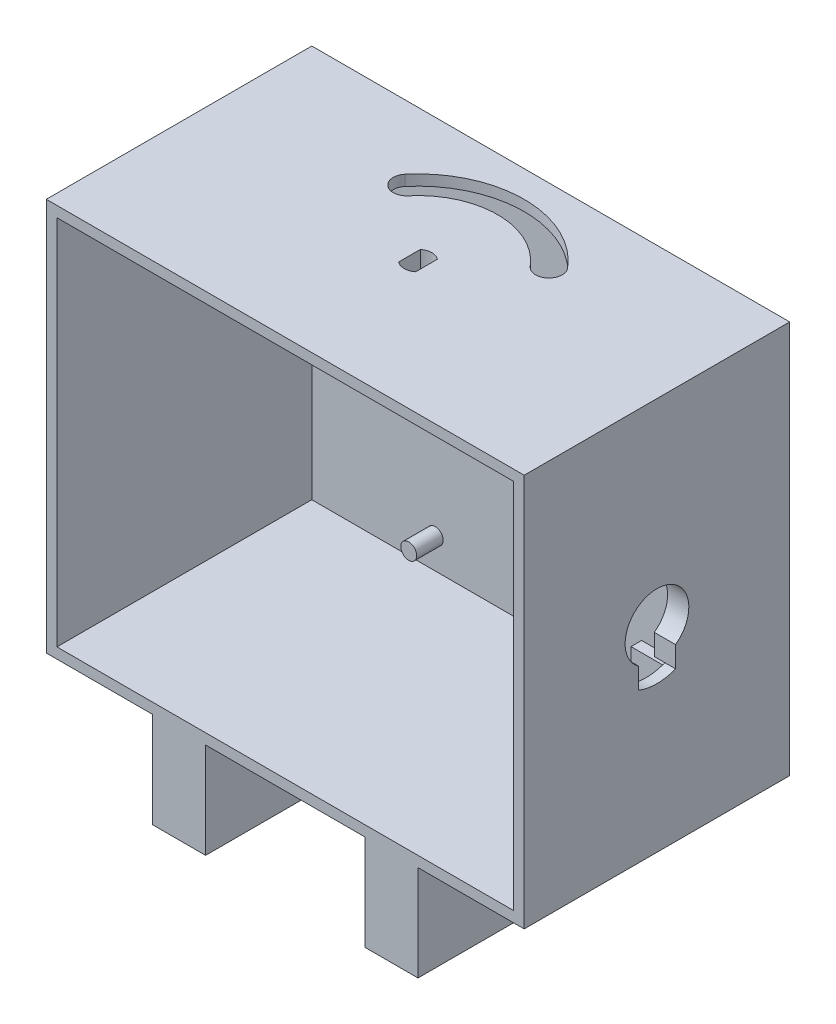
SolidWorks part; units mm, degrees
ref_plane "Front Plane" through (0, 0, 0) normal (0, 0, 1) x (1, 0, 0)
ref_plane "Top Plane" through (0, 0, 0) normal (0, 1, 0) x (1, 0, 0)
ref_plane "Right Plane" through (0, 0, 0) normal (1, 0, 0) x (0, 0, -1)
sketch "Sketch1" plane through (0, 0, 0) normal (0, 0, 1) x (1, 0, 0)
  line L0 (45, 37) -> (-45, 37)
  line L1 (43, -35) -> (-43, -35)
  line L2 (43, -35) -> (43, 35)
  line L3 (43, 35) -> (-43, 35)
  line L4 (-43, -35) -> (-43, 35)
  line L5 (43, -35) -> (-43, 35) construction
  line L6 (43, 35) -> (-43, -35) construction
  line L7 (-45, -37) -> (-45, 37)
  line L8 (45, -37) -> (-45, -37)
  line L9 (45, -37) -> (45, 37)
  line L10 (-15, -46) -> (15, -46) construction
  line L11 (-25, -37) -> (-15, -37)
  line L12 (-25, -37) -> (-25, -55)
  line L13 (-25, -55) -> (-15, -55)
  line L14 (-15, -37) -> (-15, -55)
  line L15 (15, -37) -> (25, -37)
  line L16 (15, -37) -> (15, -55)
  line L17 (15, -55) -> (25, -55)
  line L18 (25, -37) -> (25, -55)
  line L19 (0, -46) -> (0, 0) construction
  point P0 (0, 0)
  dimension "D1" = 70
  dimension "D2" = 86
  dimension "D4" = 18
  dimension "D5" = 10
  dimension "D6" = 18
  dimension "D7" = 10
  dimension "D8" = 30
  dimension "D3" = 2
extrude "Boss-Extrude1" add sketch "Sketch1" along normal mid plane 50 contours L8 L9 L0 L7 L1 L4 L3 L2 region at (43.8348, 0, 0)
extrude "Boss-Extrude2" add sketch "Sketch1<3>" against normal blind 25 from surface contours L14 L8 L12 L13 | L18 L8 L16 L17 region at (20, -46, 0) region at (-20, -46, 0) starting at face at (0, 0, 25)
sketch "Sketch1<3>" plane through (0, 0, 0) normal (0, 0, 1) x (1, 0, 0) same geometry as "Sketch1"
sketch "Sketch2" plane through (0, 0, -25) normal (0, 0, -1) x (-1, 0, 0)
  line L0 (-43, -35) -> (43, -35) construction
  line L1 (43, -35) -> (43, 35) construction
  line L2 (-43, 35) -> (43, 35) construction
  line L3 (-43, -35) -> (-43, 35) construction
  line L4 (-43, -35) -> (43, -35)
  line L5 (43, -35) -> (43, 35)
  line L6 (-43, 35) -> (43, 35)
  line L7 (-43, -35) -> (-43, 35)
extrude "Boss-Extrude3" add sketch "Sketch2" against normal blind 2
sketch "Sketch3" plane through (0, 37, 0) normal (0, 1, 0) x (1, 0, 0)
  line L1 (1.6, -2.0494) -> (-1.6, -2.0494)
  line L2 (1.6, -2.0494) -> (1.6, 2.0494)
  line L3 (1.6, 2.0494) -> (-1.6, 2.0494)
  line L4 (-1.6, -2.0494) -> (-1.6, 2.0494)
  line L5 (1.6, -2.0494) -> (-1.6, 2.0494) construction
  line L6 (1.6, 2.0494) -> (-1.6, -2.0494) construction
  circle A0 centre (0, 0) radius 2.6
  circle A1 centre (0, 0) radius 4.1
  dimension "D1" = 5.2
  dimension "D3" = 1.5
  dimension "D2" = 3.2
extrude "Cut-Extrude1" cut sketch "Sketch3" against normal up to surface (2 mm away) contours L3 A0 | L4 L1 L2 L3 | L1 A0 region at (0, 37, 2.2718) region at (0, 37, 0) region at (0, 37, -2.2718) up to face at (0, 35, 1)
extrude "Boss-Extrude4" add sketch "Sketch3<4>" against normal blind 7.5 contours A1 A0 | L2 A0 | L4 A0 region at (2.0074, 37, 0) region at (-2.0074, 37, 0) region at (-3.984, 37, 0)
sketch "Sketch3<4>" plane through (0, 37, 0) normal (0, 1, 0) x (1, 0, 0) same geometry as "Sketch3"
sketch "Sketch4" plane through (45, 0, 0) normal (1, 0, 0) x (0, 0, -1)
  line L0 (0, -6) -> (0, -9.5) construction
  line L1 (3.5, -4.8734) -> (3.5, -8.8318)
  line L2 (-3.5, -4.8734) -> (-3.5, -8.8318)
  line L3 (0, -23) -> (0, -9.5) construction
  line L4 (8.1, 10.5) -> (-8.1, 10.5)
  line L5 (8.1, 10.5) -> (8.1, 12.5)
  line L6 (8.1, 12.5) -> (-8.1, 12.5)
  line L7 (-8.1, 10.5) -> (-8.1, 12.5)
  line L8 (8.1, 10.5) -> (-8.1, 12.5) construction
  line L9 (8.1, 12.5) -> (-8.1, 10.5) construction
  line L10 (8.1, -24) -> (-8.1, -24)
  line L11 (8.1, -24) -> (8.1, -22)
  line L12 (8.1, -22) -> (-8.1, -22)
  line L13 (-8.1, -24) -> (-8.1, -22)
  line L14 (8.1, -24) -> (-8.1, -22) construction
  line L15 (8.1, -22) -> (-8.1, -24) construction
  line L16 (-8.1, -22) -> (-6.1, -22)
  line L17 (-8.1, -22) -> (-8.1, -12)
  line L18 (-8.1, -12) -> (-6.1, -12)
  line L19 (-6.1, -22) -> (-6.1, -12)
  line L20 (8.1, -12) -> (6.1, -12)
  line L21 (-8.1, 10.5) -> (-6.1, 10.5)
  line L22 (-8.1, 10.5) -> (-8.1, 8.5)
  line L23 (-8.1, 8.5) -> (-6.1, 8.5)
  line L24 (-6.1, 10.5) -> (-6.1, 8.5)
  line L25 (6.1, -22) -> (6.1, -12)
  line L26 (8.1, -22) -> (6.1, -22)
  line L27 (8.1, -22) -> (8.1, -12)
  line L28 (8.1, 8.5) -> (6.1, 8.5)
  line L29 (6.1, 10.5) -> (6.1, 8.5)
  line L30 (8.1, 10.5) -> (6.1, 10.5)
  line L31 (8.1, 10.5) -> (8.1, 8.5)
  circle A0 centre (0, 0) radius 6
  circle A1 centre (0, 0) radius 9.5
  point P10 (0, 11.5)
  point P16 (0, -23)
  dimension "D1" = 12
  dimension "D2" = 3.5
  dimension "D3" = 7
  dimension "D4" = 10.5
  dimension "D5" = 16.2
  dimension "D6" = 2
  dimension "D7" = 32.5
  dimension "D8" = 2
  dimension "D9" = 10
  dimension "D10" = 2
extrude "Cut-Extrude2" cut sketch "Sketch4" against normal up to surface (2 mm away) contours A0 | L2 A1 L1 A0 region at (45, -7.4505, 0) region at (45, 0, 0) up to face at (43, 0, 1)
extrude "Boss-Extrude5" add sketch "Sketch4<3>" against normal blind 2 from surface contours L1 A1 L2 A0 region at (45, -2.8591, -5.5735) starting at face at (43, -4.3013, 0)
sketch "Sketch4<3>" plane through (45, 0, 0) normal (1, 0, 0) x (0, 0, -1) same geometry as "Sketch4"
extrude "Boss-Extrude6" add sketch "Sketch4<4>" against normal blind 9 from surface contours L7 L4 L5 L6 | L12 L19 L18 L17 | L13 L10 L11 L12 | L12 L27 L20 L25 | L24 L4 L22 L23 | L31 L4 L29 L28 region at (45, 9.5, -7.1) region at (45, 11.5, 0) region at (45, 9.5, 7.1) region at (45, -23, 0) region at (45, -17, -7.1) region at (45, -17, 7.1) starting at face at (43, 0, 1)
sketch "Sketch4<4>" plane through (45, 0, 0) normal (1, 0, 0) x (0, 0, -1) same geometry as "Sketch4"
sketch "Sketch6" plane through (0, 0, -23) normal (0, 0, 1) x (1, 0, 0)
  line L1 (34.5, -31.5) -> (-40.5, -31.5) construction
  line L2 (34.5, -31.5) -> (34.5, 21.5) construction
  line L3 (34.5, 21.5) -> (-40.5, 21.5) construction
  line L4 (-40.5, -31.5) -> (-40.5, 21.5) construction
  line L5 (34.5, -31.5) -> (-40.5, 21.5) construction
  line L6 (34.5, 21.5) -> (-40.5, -31.5) construction
  circle A0 centre (32.25, 3.5) radius 1.5
  circle A1 centre (-18.75, 19.25) radius 1.5
  circle A2 centre (-19.75, -29.25) radius 1.5
  circle A3 centre (32.25, -24) radius 1.5
  point P0 (-3, -5)
  dimension "D3" = 3
  dimension "D1" = 75
  dimension "D2" = 53
  dimension "D4" = 2.25
  dimension "D5" = 2.25
  dimension "D6" = 2.25
  dimension "D7" = 51
  dimension "D8" = 52
  dimension "D9" = 7.5
  dimension "D10" = 27.5
  dimension "D11" = 5.831
  dimension "D12" = 5
  dimension "D13" = 3
extrude "Boss-Extrude7" add sketch "Sketch6" along normal blind 5
sketch "Sketch7" plane through (-45, 0, 0) normal (-1, 0, 0) x (0, 0, 1)
  arc A0 (3.5, -4.8734) -> (-3.5, -4.8734) centre (0, 0) ccw construction
  arc A1 (3.5, -4.8734) -> (-3.5, -4.8734) centre (0, 0) ccw
  circle A2 centre (0, 0) radius 2.5
  dimension "D1" = 5
extrude "Boss-Extrude8" add sketch "Sketch7" along normal blind 3 contours A2 region at (-45, 0, 0)
sketch "Sketch8" plane through (0, 35, 0) normal (0, -1, 0) x (1, 0, 0)
  line L0 (0, 0) -> (-15.3209, -12.8558)
  line L1 (0, 0) -> (15.3209, -12.8558)
  circle A0 centre (0, 0) radius 20
  circle A1 centre (0, 0) radius 15
  arc A2 (15.3209, -12.8558) -> (11.4907, -9.6418) centre (13.4058, -11.2488) ccw
  arc A3 (-15.3209, -12.8558) -> (-11.4907, -9.6418) centre (-13.4058, -11.2488) cw
  point P10 (0, 0)
  point P11 (0, 0)
  point P12 (0, 0)
  point P13 (0, 0)
  dimension "D1" = 40
  dimension "D2" = 30
  dimension "D3" = 100
extrude "Cut-Extrude3" cut sketch "Sketch8" against normal through all contours A1 L0 A0 L1 | A3 L0 | L1 A2 region at (0, 35, -15.4664) region at (-14.0878, 35, -10.436) region at (14.0878, 35, -10.436)
